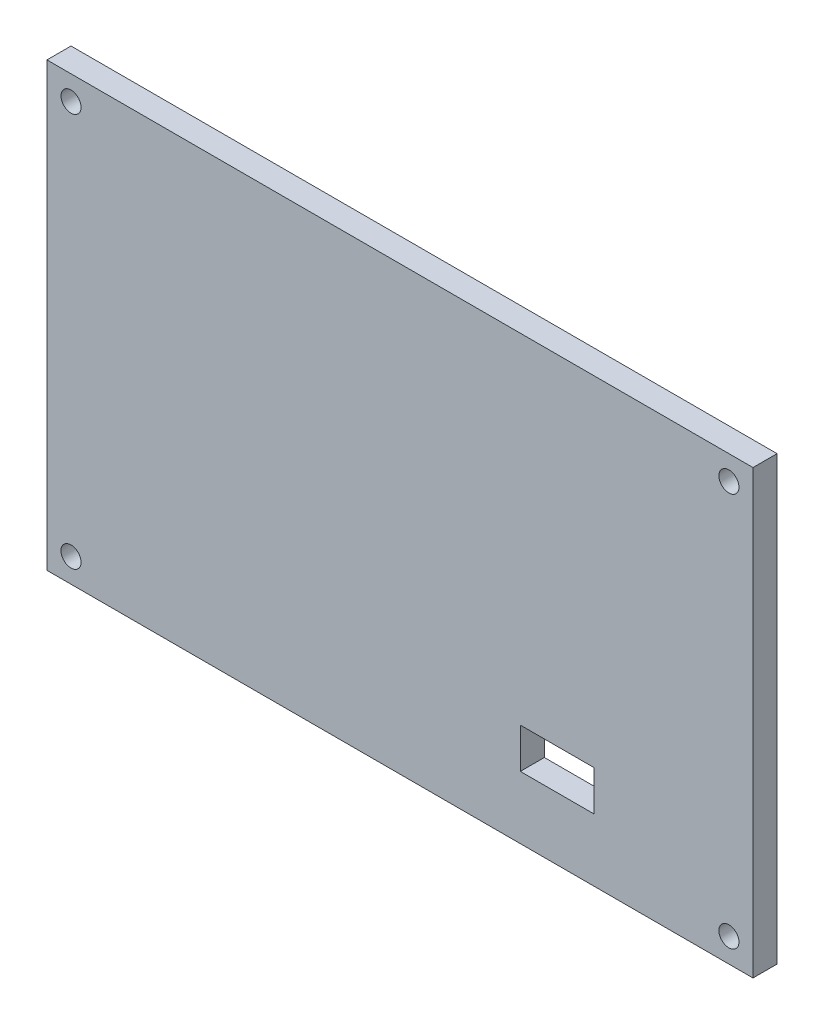
SolidWorks part; units mm, degrees
ref_plane "前视基准面" through (0, 0, 0) normal (0, 0, 1) x (1, 0, 0)
ref_plane "上视基准面" through (0, 0, 0) normal (0, 1, 0) x (1, 0, 0)
ref_plane "右视基准面" through (0, 0, 0) normal (1, 0, 0) x (0, 0, -1)
other "Configuration Table"
sketch "草图1" plane through (0, 0, 0) normal (0, 0, 1) x (1, 0, 0)
  line L9 (-88, 27.55) -> (0, 27.55)
  line L10 (-88, 27.55) -> (-88, -27.55)
  line L16 (-88, -27.55) -> (0, -27.55)
  line L17 (0, 27.55) -> (0, -27.55)
  point P4 (-88, -30.492)
  point P5 (0, 0)
  dimension "D2" = 88
  dimension "D1" = 55.1
extrude "凸台-拉伸1" add sketch "草图1" along normal blind 3 contours L16 L17 L9 L10
sketch "草图2" plane through (0, 0, 0) normal (0, 0, -1) x (-1, 0, 0)
  line L0 (88, 27.55) -> (0, 27.55) construction
  line L1 (0, 27.55) -> (0, -27.55) construction
  line L2 (88, 27.55) -> (88, -27.55) construction
  line L3 (88, -27.55) -> (0, -27.55) construction
  circle A0 centre (3, 24.55) radius 2
  circle A1 centre (85, 24.55) radius 2
  circle A2 centre (3, -24.55) radius 2
  circle A3 centre (85, -24.55) radius 2
  circle A4 centre (3, 24.55) radius 1.25
  circle A5 centre (3, -24.55) radius 1.25
  circle A6 centre (85, -24.55) radius 1.25
  circle A7 centre (85, 24.55) radius 1.25
  point P20 (0, 0)
  point P21 (0, 0)
  point P22 (0, 0)
  point P23 (0, 0)
  dimension "D1" = 2.5
  dimension "D2" = 4
  dimension "D3" = 3
  dimension "D4" = 3
  dimension "D5" = 3
  dimension "D6" = 3
extrude "切除-拉伸1" cut sketch "草图2" against normal through all contours A5 | A6 | A7 | A4
extrude "切除-拉伸2" cut sketch "草图2<3>" against normal blind 1 contours A0 | A1 | A3 | A2
sketch "草图2<3>" plane through (0, 0, 0) normal (0, 0, -1) x (-1, 0, 0) same geometry as "草图2"
sketch "草图3" plane through (0, 0, 0) normal (0, 0, -1) x (-1, 0, 0)
  line L0 (0, 27.55) -> (0, -27.55) construction
  line L1 (19.8, -14.75) -> (29, -14.75)
  line L2 (19.8, -14.75) -> (19.8, -19.75)
  line L3 (19.8, -19.75) -> (29, -19.75)
  line L4 (29, -14.75) -> (29, -19.75)
  line L5 (88, -27.55) -> (0, -27.55) construction
  dimension "D1" = 19.8
  dimension "D2" = 7.8
  dimension "D3" = 5
  dimension "D4" = 9.2
extrude "切除-拉伸3" cut sketch "草图3" against normal through all
